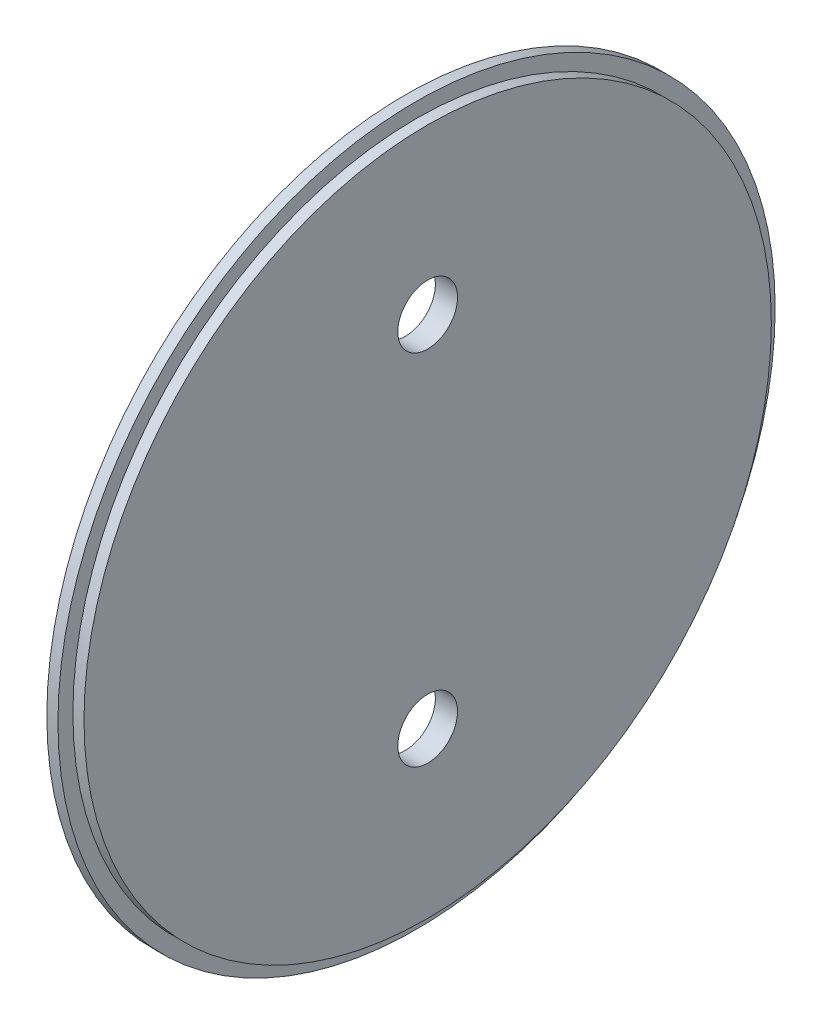
SolidWorks part; units mm, degrees
ref_plane "Front Plane" through (0, 0, 0) normal (1, 0, 0) x (0, 1, 0)
ref_plane "Top Plane" through (0, 0, 0) normal (0, 0, 1) x (0, 1, 0)
ref_plane "Right Plane" through (0, 0, 0) normal (0, 1, 0) x (-1, 0, 0)
sketch "Sketch1" plane through (0, 0, 0) normal (1, 0, 0) x (0, 1, 0)
  circle A0 centre (0, 0) radius 38.1
  dimension "D1" = 76.2
extrude "Boss-Extrude1" add sketch "Sketch1" along normal blind 1.1811
sketch "Sketch2" plane through (1.1811, 0, 0) normal (1, 0, 0) x (0, 1, 0)
  circle A0 centre (0, 0) radius 36.5125
  dimension "D1" = 73.025
extrude "Boss-Extrude2" add sketch "Sketch2" along normal blind 1.1811
sketch "Sketch3" plane through (0, 0, 0) normal (-1, 0, 0) x (0, -1, 0)
  circle A1 centre (19.05, 0) radius 3.175
  circle A2 centre (-19.05, 0) radius 3.175
  point P0 (0, 0)
  point P2 (0.8932, -0.1935)
  point P7 (0, 0)
  dimension "D1" = 19.05
  dimension "D2" = 6.35
  dimension "D3" = 6.35
  dimension "D4" = 19.05
extrude "Cut-Extrude1" cut sketch "Sketch3" against normal through all
